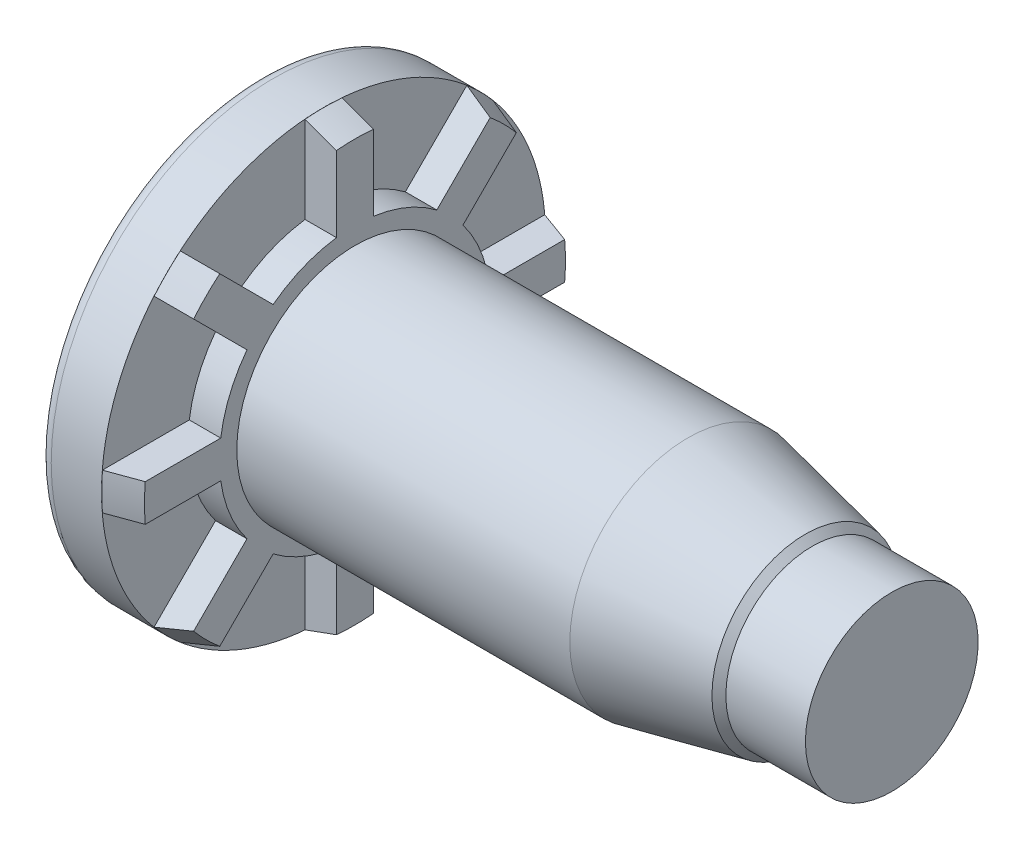
SolidWorks part; units mm, degrees
revolve "BaseBody" add sketch "BodySke" angle 360 about L6 other way angle 7.5
sketch "BodySke" plane through (0, 0, 0) normal (0, 0, 1) x (1, 0, 0)
  line L0 (-2.1082, 7.0206) -> (-2.1082, 0)
  line L1 (1.0541, 7.0569) -> (1.0541, 3.9624)
  line L2 (0.0025, 7.4397) -> (1.0541, 7.0569)
  line L3 (1.0541, 3.9624) -> (12.2174, 3.9624)
  line L4 (12.2174, 3.9624) -> (16.1493, 3.1293)
  line L5 (19.05, 0) -> (-2.1082, 0)
  line L6 (0, 0) -> (50.554, 0) construction
  line L7 (16.383, 2.8956) -> (19.05, 2.8956)
  line L8 (16.383, 2.8956) -> (16.1493, 3.1293)
  line L9 (-1.6866, 7.4422) -> (0, 7.4422)
  line L10 (0.0025, 7.4397) -> (0, 7.4397)
  line L11 (1.4097, 19.05) -> (1.4097, -3.175) construction
  line L12 (0, 7.4397) -> (0, 7.4422)
  line L13 (19.05, 2.8956) -> (19.05, 0)
  arc A0 (-2.1082, 7.0206) -> (-1.6866, 7.4422) centre (-1.6866, 7.0206) cw
  dimension "Fillet_rad" = 0.4216
  dimension "T_dim" = 2.1082
  dimension "H_dia" = 14.8844
  dimension "D2" = 0.0025
  dimension "D3" = 0.0025
  dimension "Advance" = 1.4097
  dimension "D1" = 20
  dimension "Length" = 19.05
  dimension "D4" = 45
  dimension "Diameter" = 7.9248
  dimension "Minor_dia" = 6.2586
cosmetic thread "ThreadCosmetic" [suppressed] parameters "Thread_length"=12.2123, "Thread_minor"=6.2586
ref_plane "Plane1" through (0, 0, 0) normal (0, 0, 1) x (1, 0, 0)
ref_plane "Plane2" through (0, 0, 0) normal (0, 1, 0) x (1, 0, 0)
ref_plane "Plane3" through (0, 0, 0) normal (1, 0, 0) x (0, 0, -1)
sketch "ThdSchSke" plane through (0, 0, 0) normal (0, 0, 1) x (1, 0, 0)
  line L0 (3.937, -3.1293) -> (3.3536, -3.9624)
  line L1 (3.937, -3.1293) -> (4.5204, -3.9624)
  line L2 (4.5204, -3.9624) -> (4.5204, -4.953)
  line L3 (-3.175, 0) -> (5.1513, 0) construction
  line L4 (0, -7.4422) -> (0, 7.4422) construction
  line L5 (4.5204, -4.953) -> (3.3536, -4.953)
  line L6 (3.3536, -4.953) -> (3.3536, -3.9624)
  line L7 (21.9888, 6.5809) -> (21.9888, 1.1961) construction
  dimension "Diameter" = 7.9248
  dimension "Thread_minor" = 6.2586
  dimension "Start" = 3.937
revolve "ThreadSchematic" [suppressed] cut sketch "ThdSchSke" angle 360 about L3
pattern_linear "ThdSchPat" [suppressed]
sketch "RibCutSke" plane through (1.0541, 1.7944, -0.091) normal (1, 0, 0) x (0, 0, -1)
  line L0 (0.5289, 2.7055) -> (0.5289, 5.6219)
  line L1 (2.6526, 1.8258) -> (4.7149, 3.888)
  line L2 (0.5289, 2.1192) -> (0.5289, 2.4006) construction
  line L3 (-0.091, -1.7944) -> (-0.091, 5.0239) construction
  line L4 (-0.091, -1.7944) -> (0.5289, 2.1192) construction
  line L5 (-0.091, -1.7944) -> (2.2381, 1.4112) construction
  line L6 (2.2381, 1.4112) -> (2.4421, 1.6153) construction
  arc A1 (2.6526, 1.8258) -> (0.5289, 2.7055) centre (-0.091, -1.7944) ccw
  arc A2 (4.7149, 3.888) -> (0.5289, 5.6219) centre (-0.091, -1.7944) ccw
  circle A3 centre (-0.091, -1.7944) radius 7.0569 construction
  circle A4 centre (-0.091, -1.7944) radius 3.9624 construction
  dimension "Rib_root_half_angle" = 9
  dimension "Rib_root_gap_angle" = 27
  dimension "Angle" = 45
extrude "RibCut" cut sketch "RibCutSke" against normal blind 1.0541
pattern_circular "RibCutsPat" count 8 every 45 about axis through (0, 0, 0) along (1, 0, 0) of "RibCut"
equation "' \"Length@BodySke\" = 0.75"
equation "' \"H_dia@BodySke\" = 0.586"
equation "' \"Start@ThdSchSke\" = 0.155"
equation "' \"T_dim@BodySke\" = 0.083"
equation "' \"Dog_dia@BodySke\" = 0.228"
equation "' \"Dog_len@BodySke\" = 0.105"
equation "' \"Thread_trans@BodySke\" = 0.164"
equation "' \"Diameter@BodySke\" = 0.312"
equation "' \"Minor_dia@BodySke\" =  0.2464"
equation "' \"Minor_dia@BodySke\" = 0.2464"
equation "' \"Advance@BodySke\" = 0.0555"
equation "\"Fillet_rad@BodySke\" =  \"T_dim@BodySke\" * 0.2"
equation "\"Clinch_ht@BodySke\" = \"T_dim@BodySke\" * 0.5"
equation "\"Num_ribs@RibCutsPat\" = 8"
equation "\"Angle@RibCutSke\" =\"Angle@RibCutsPat\""
equation "\"Rib_root_half_angle@RibCutSke\" = \"Angle@RibCutSke\" / 5"
equation "\"Rib_root_gap_angle@RibCutSke\" = \"Angle@RibCutSke\" - (2 * \"Rib_root_half_angle@RibCutSke\" )"
equation "\"Rib_root_dia@RibCutSke\" = \"Diameter@BodySke\""
equation "\"Inner_dia@RibCutSke\" = \"Diameter@BodySke\" + ( \"H_dia@BodySke\" - \"Diameter@BodySke\" ) / 6"
equation "\"Outer_dia@RibCutSke\" = \"H_dia@BodySke\""
equation "\"Depth@RibCut\" = \"Clinch_ht@BodySke\""
equation "\"Thread_length@ThreadCosmetic\" = \"Length@BodySke\" - \"Start@ThdSchSke\"  - \"Dog_len@BodySke\"  - ( \"Minor_dia@BodySke\" - \"Dog_dia@BodySke\" ) / 2"
equation "\"Thread_minor@ThreadCosmetic\" = \"Minor_dia@BodySke\""
equation "\"Thread_minor@ThdSchSke\" = \"Minor_dia@BodySke\""
equation "\"Diameter@ThdSchSke\" = \"Diameter@BodySke\""
equation "\"Overcut@ThdSchSke\" = \"Diameter@BodySke\" * 1.25"
equation "\"Num_threads@ThdSchPat\" = int( \"Thread_length@ThreadCosmetic\" / \"Advance@BodySke\" + 0.999 )  + 1"
equation "\"Advance@ThdSchPat\" = \"Thread_length@ThreadCosmetic\" /  (\"Num_threads@ThdSchPat\" - 1) 'relax it"
equation "\"Num_threads@ThdSchPat\" = \"Num_threads@ThdSchPat\" - sgn( \"Num_threads@ThdSchPat\" - 1) '---chamfered tips only---"
